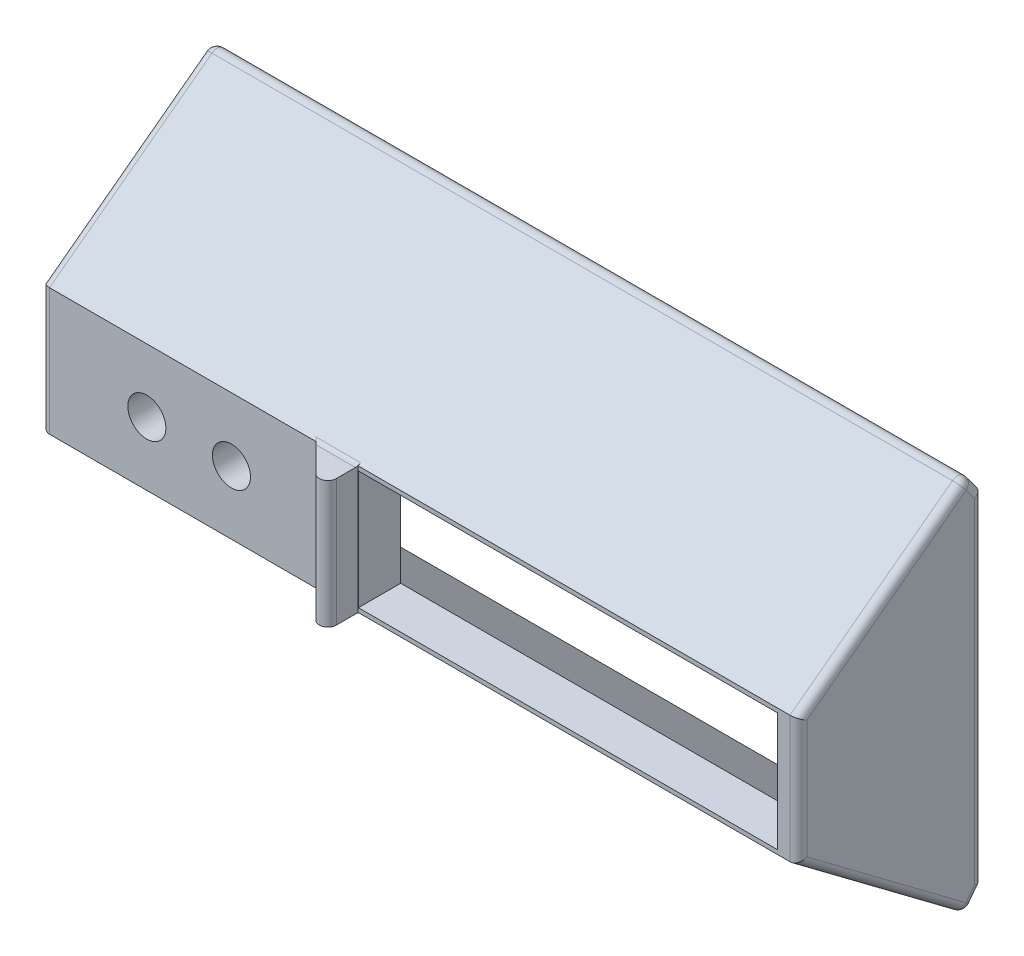
SolidWorks part; units mm, degrees
ref_plane "Front Plane" through (0, 0, 0) normal (1, 0, 0) x (0, 1, 0)
ref_plane "Top Plane" through (0, 0, 0) normal (0, 0, 1) x (0, 1, 0)
ref_plane "Right Plane" through (0, 0, 0) normal (0, 1, 0) x (-1, 0, 0)
sketch "Sketch1" plane through (0, 0, 0) normal (1, 0, 0) x (0, 1, 0)
  line L0 (-7.5, -2.5) -> (-20.1, -19.3)
  line L1 (-7.5, 2.5) -> (7.5, 2.5)
  line L2 (-7.5, 2.5) -> (-7.5, -2.5)
  line L3 (-7.5, -2.5) -> (7.5, -2.5)
  line L4 (7.5, 2.5) -> (7.5, -2.5)
  line L5 (-7.5, 2.5) -> (7.5, -2.5) construction
  line L6 (-7.5, -2.5) -> (7.5, 2.5) construction
  line L7 (-20.1, -19.3) -> (-22.5, -17.5)
  line L8 (-22.5, -17.5) -> (-7.5, 2.5)
  line L9 (0, -2.5) -> (0, 2.5) construction
  line L10 (22.5, -17.5) -> (7.5, 2.5)
  line L11 (20.1, -19.3) -> (22.5, -17.5)
  line L12 (7.5, -2.5) -> (20.1, -19.3)
  point P0 (0, 0)
  point P12 (0, 0)
  point P13 (46.6441, -13.5819)
  point P14 (-41.7547, -17.2204)
  point P15 (-14.9129, -12.6275)
  point P16 (-19.5407, -14.9221)
  dimension "D1" = 20
  dimension "D2" = 15
  dimension "D3" = 5
  dimension "D4" = 15
extrude "Boss-Extrude1" add sketch "Sketch1" along normal blind 80 contours L8 L7 L0 L2 | L4 L1 L2 L3 | L4 L12 L11 L10 region at (0, -14.4174, -9.1507) region at (0, 0, 0) region at (0, 14.4174, -9.1507)
sketch "Sketch2" plane through (0, 0, 2.5) normal (0, 0, 1) x (1, 0, 0)
  line L0 (80, -7.5) -> (80, 7.5) construction
  line L1 (80, 7) -> (30.5, 7)
  line L2 (80, 7) -> (80, -7)
  line L3 (80, -7) -> (30.5, -7)
  line L4 (30.5, 7) -> (30.5, -7)
  line L5 (80, 7) -> (30.5, -7) construction
  line L6 (80, -7) -> (30.5, 7) construction
  line L7 (0, 0) -> (55.25, 0) construction
  line L8 (0, -7.5) -> (0, 7.5) construction
  circle A0 centre (5.5, 0) radius 2.25
  circle A1 centre (15.5, 0) radius 2.25
  point P4 (55.25, 0)
  point P14 (15.8582, 0)
  dimension "D3" = 4.5
  dimension "D1" = 14
  dimension "D2" = 10
  dimension "D4" = 5.5
  dimension "D5" = 15
extrude "Cut-Extrude1" cut sketch "Sketch2" against normal through all
sketch "Sketch3" plane through (0, 0, 2.5) normal (0, 0, 1) x (1, 0, 0)
  line L0 (80, 7.5) -> (0, 7.5) construction
  line L1 (30.4776, 7.5) -> (22.4776, 7.5)
  line L2 (30.4776, 7.5) -> (30.4776, -7.5)
  line L3 (30.4776, -7.5) -> (22.4776, -7.5)
  line L4 (22.4776, 7.5) -> (22.4776, -7.5)
  line L5 (30.4776, 7.5) -> (22.4776, -7.5) construction
  line L6 (30.4776, -7.5) -> (22.4776, 7.5) construction
  line L7 (80, -7.5) -> (0, -7.5) construction
  point P4 (26.4776, 0)
  dimension "D1" = 8
extrude "Boss-Extrude2" add sketch "Sketch3" along normal blind 5
chamfer "Chamfer1" distance 8 angle 45 1 edges at (22.4776, 0, 7.5)
fillet "Fillet1" radius 1 5 edges at (40, -7.5, -2.5) (40, 7.5, -2.5) (27.9776, 7.5, 2.5) (27.9776, -7.5, 2.5) (30.4776, 0, 7.5)
sketch "Sketch4" plane through (0, 0, 0) normal (-1, 0, 0) x (0, -1, 0)
  line L8 (22.5, -17.5) -> (7.5, 2.5)
  line L9 (7.5, 2.5) -> (-7.5, 2.5)
  line L10 (-7.5, 2.5) -> (-22.5, -17.5)
  line L11 (-22.5, -17.5) -> (-20.1, -19.3)
  line L12 (-20.1, -19.3) -> (-7.8, -2.9)
  line L13 (-7, -2.5) -> (7, -2.5)
  line L14 (7.8, -2.9) -> (20.1, -19.3)
  line L15 (20.1, -19.3) -> (22.5, -17.5)
  line L16 (22.5, -17.5) -> (7.5, 2.5)
  line L17 (7.5, 2.5) -> (-7.5, 2.5)
  line L18 (-7.5, 2.5) -> (-22.5, -17.5)
  line L19 (-22.5, -17.5) -> (-20.1, -19.3)
  line L20 (-20.1, -19.3) -> (-7.8, -2.9)
  line L21 (-7, -2.5) -> (7, -2.5)
  line L22 (7.8, -2.9) -> (20.1, -19.3)
  line L23 (20.1, -19.3) -> (22.5, -17.5)
  arc A2 (-7, -2.5) -> (-7.8, -2.9) centre (-7, -3.5) ccw
  arc A3 (7.8, -2.9) -> (7, -2.5) centre (7, -3.5) ccw
  arc A4 (-7, -2.5) -> (-7.8, -2.9) centre (-7, -3.5) ccw
  arc A5 (7.8, -2.9) -> (7, -2.5) centre (7, -3.5) ccw
  dimension "D1" = 0
extrude "Boss-Extrude3" add sketch "Sketch4" along normal blind 7
sketch "Sketch6" plane through (80, 0, 0) normal (1, 0, 0) x (0, 1, 0)
  line L0 (7, 2.5) -> (7, -2.5) construction
  line L1 (7.8, -2.9) -> (20.1, -19.3) construction
  line L2 (20.1, -19.3) -> (22.5, -17.5) construction
  line L3 (22.5, -17.5) -> (7.5, 2.5) construction
  line L4 (7.5, 2.5) -> (7, 2.5) construction
  line L5 (-7, -2.5) -> (-7, 2.5) construction
  line L6 (-7, 2.5) -> (-7.5, 2.5) construction
  line L7 (-7.5, 2.5) -> (-22.5, -17.5) construction
  line L8 (-22.5, -17.5) -> (-20.1, -19.3) construction
  line L9 (-20.1, -19.3) -> (-7.8, -2.9) construction
  line L10 (7, 2.5) -> (7, -2.5)
  line L11 (7.8, -2.9) -> (20.1, -19.3)
  line L12 (20.1, -19.3) -> (22.5, -17.5)
  line L13 (22.5, -17.5) -> (7.5, 2.5)
  line L14 (7.5, 2.5) -> (7, 2.5)
  line L15 (-7, -2.5) -> (-7, 2.5)
  line L16 (-7, 2.5) -> (-7.5, 2.5)
  line L17 (-7.5, 2.5) -> (-22.5, -17.5)
  line L18 (-22.5, -17.5) -> (-20.1, -19.3)
  line L19 (-20.1, -19.3) -> (-7.8, -2.9)
  line L20 (-20.1, -19.3) -> (20.1, -19.3)
  line L21 (-7, 2.5) -> (7, 2.5)
  arc A0 (7.8, -2.9) -> (7, -2.5) centre (7, -3.5) ccw construction
  arc A1 (-7, -2.5) -> (-7.8, -2.9) centre (-7, -3.5) ccw construction
  arc A2 (7.8, -2.9) -> (7, -2.5) centre (7, -3.5) ccw
  arc A3 (-7, -2.5) -> (-7.8, -2.9) centre (-7, -3.5) ccw
  line M1 (7, 2.5) -> (7, -2.5)
  arc M2 (7, -2.5) -> (7.8, -2.9) centre (7, -3.5) cw
  line M3 (7.8, -2.9) -> (20.1, -19.3)
  line M4 (20.1, -19.3) -> (22.5, -17.5)
  line M5 (22.5, -17.5) -> (7.5, 2.5)
  line M6 (7.5, 2.5) -> (7, 2.5)
extrude "Boss-Extrude4" add sketch "Sketch6" along normal blind 2.5 contours L15 A3 L19 L20 L21 M3 M2 M1 | A3 L15 L16 L17 L18 L19 | M6 M1 M2 M3 M4 M5 region at (80, 14.1634, -8.8276) region at (80, 0, -10.582) region at (80, -14.1634, -8.8276)
fillet "Fillet3" radius 1 18 edges at (-7, -13.95, -11.1) (-7, -7.4472, -2.6056) (-7, 0, -2.5) (-7, 7.4472, -2.6056) (-7, 13.95, -11.1) (-7, 21.3, -18.4) (-7, 15, -7.5) (-7, 0, 2.5) (-7, -15, -7.5) (-7, -21.3, -18.4) (82.5, 15, -7.5) (82.5, 21.3, -18.4) (82.5, 0, -19.3) (82.5, -21.3, -18.4) (82.5, -15, -7.5) (82.5, 0, 2.5) (37.75, 22.5, -17.5) (37.75, -22.5, -17.5)
